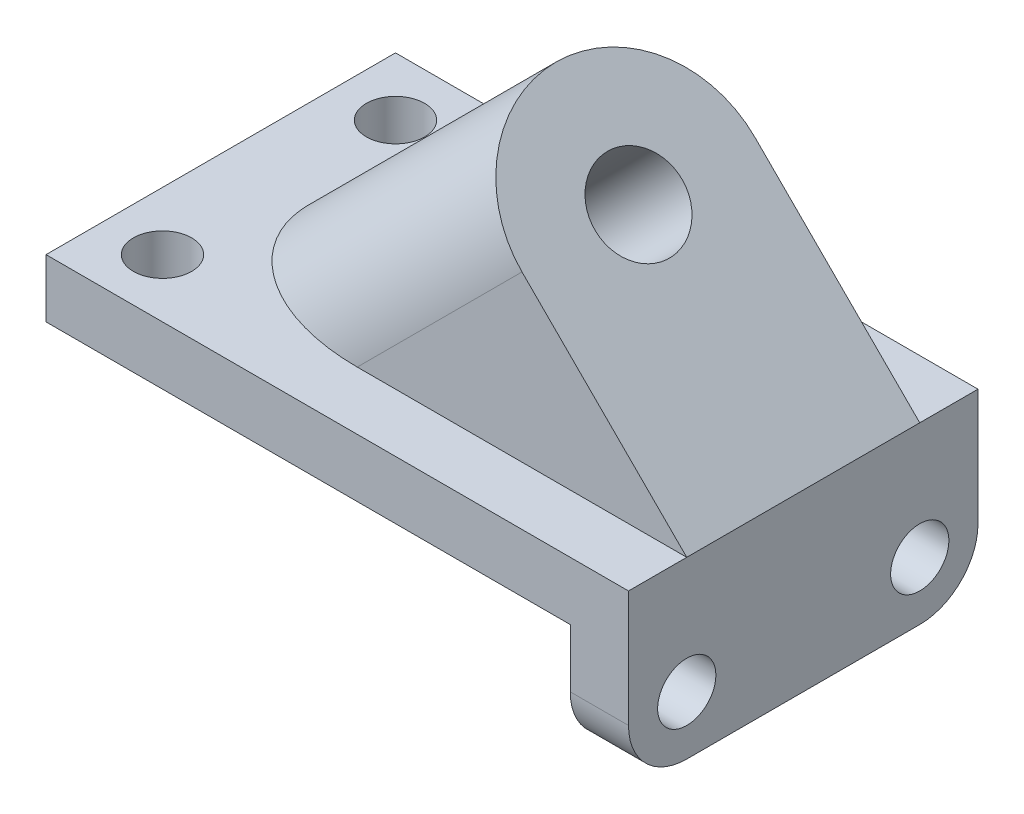
SolidWorks part; units mm, degrees
ref_plane "Front Plane" through (0, 0, 0) normal (0, 0, 1) x (1, 0, 0)
ref_plane "Top Plane" through (0, 0, 0) normal (0, 1, 0) x (1, 0, 0)
ref_plane "Right Plane" through (0, 0, 0) normal (1, 0, 0) x (0, 0, -1)
sketch "Sketch1" plane through (0, 0, 0) normal (0, 1, 0) x (1, 0, 0)
  line L1 (0, 0) -> (127, 0)
  line L2 (0, 0) -> (0, 76.2)
  line L3 (0, 76.2) -> (127, 76.2)
  line L4 (127, 0) -> (127, 76.2)
  line L5 (0, 0) -> (127, 76.2) construction
  line L6 (0, 76.2) -> (127, 0) construction
  circle A0 centre (12.7, 12.7) radius 6.35
  circle A1 centre (12.7, 63.5) radius 6.35
  point P4 (63.5, 38.1)
  dimension "D1" = 12.7
  dimension "D4" = 50.8
  dimension "D2" = 76.2
  dimension "D6" = 12.7
  dimension "D3" = 12.7
  dimension "D5" = 127
  dimension "D7" = 12.7
  dimension "D8" = 12.7
extrude "Boss-Extrude1" add sketch "Sketch1" against normal blind 12.7
sketch "Sketch7" plane through (127, 0, 0) normal (1, 0, 0) x (0, 0, -1)
  line L0 (0, 0) -> (76.2, 0) construction
  line L1 (0, 0) -> (76.2, 0)
  line L2 (0, 0) -> (0, -25.4)
  line L3 (12.7, -38.1) -> (63.5, -38.1)
  line L4 (76.2, 0) -> (76.2, -25.4)
  line L5 (0, 0) -> (76.2, -38.1) construction
  line L6 (0, -38.1) -> (76.2, 0) construction
  circle A0 centre (12.7, -25.4) radius 6.35
  circle A1 centre (63.5, -25.4) radius 6.35
  arc A2 (63.5, -38.1) -> (76.2, -25.4) centre (63.5, -25.4) ccw
  arc A3 (0, -25.4) -> (12.7, -38.1) centre (12.7, -25.4) ccw
  point P4 (38.1, -19.05)
  dimension "D1" = 12.7
  dimension "D2" = 12.7
  dimension "D5" = 12.7
  dimension "D6" = 12.7
  dimension "D3" = 38.1
  dimension "D4" = 25.4
  dimension "D7" = 38.1
  dimension "D9" = 76.2
extrude "Boss-Extrude5" add sketch "Sketch7" against normal blind 12.7
ref_plane "Plane1" through (63.5, 63.5, 0) normal (0.7071, 0.7071, 0) x (0, 0, -1)
sketch "Sketch9" plane through (63.5, 63.5, 0) normal (0.7071, 0.7071, 0) x (0, 0, -1)
  line L0 (12.7, -89.8026) -> (63.5, -89.8026)
  line L1 (0, -89.8026) -> (76.2, -89.8026) construction
  line L5 (63.5, -89.8026) -> (63.5, -39.0026)
  line L6 (12.7, -89.8026) -> (12.7, -39.0026)
  arc A0 (12.7, -39.0026) -> (63.5, -39.0026) centre (38.1, -39.0026) cw
  point P0 (0, 0)
  point P1 (0, 0)
  dimension "D1" = 12.7
  dimension "D3" = 25.4
extrude "Boss-Extrude9" add sketch "Sketch9" against normal up to surface contours L0 L5 A0 L6 up to face at (63.5, 0, -38.1)
sketch "Sketch13" plane through (63.5, 63.5, 0) normal (0.7071, 0.7071, 0) x (0, 0, -1)
  line L0 (12.7, -89.8026) -> (63.5, -89.8026) construction
  circle A0 centre (38.1, -39.0026) radius 9.525
  point P0 (38.1, -39.0026)
  dimension "D1" = 50.8
  dimension "D2" = 19.05
  dimension "D3" = 38.1
extrude "Cut-Extrude1" cut sketch "Sketch13" against normal blind 101.6
